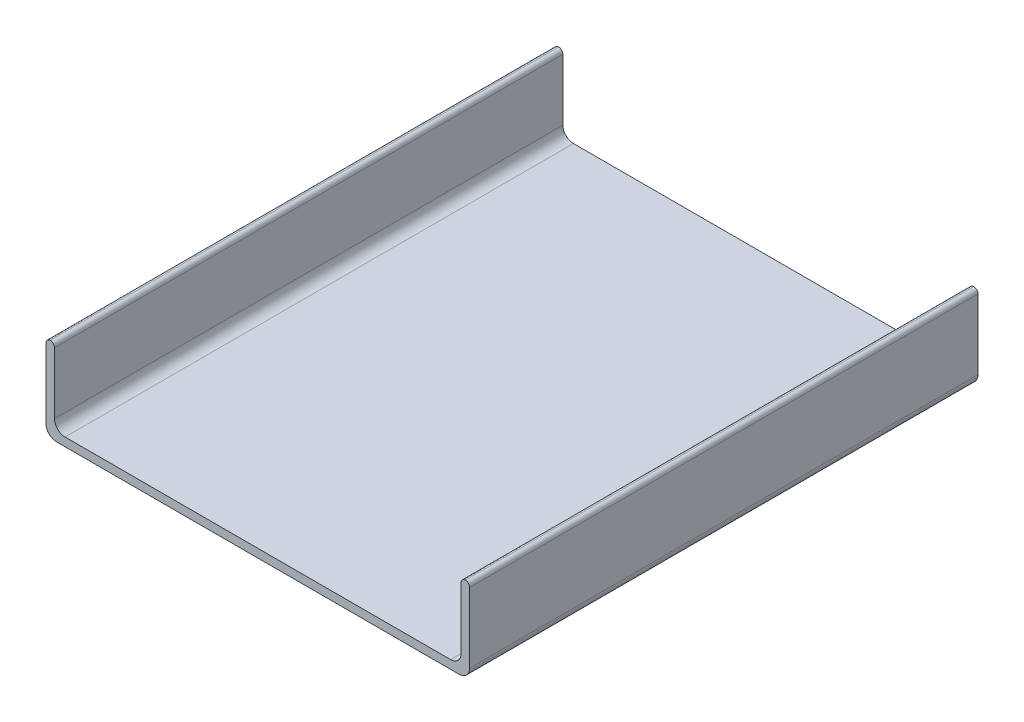
SolidWorks part; units mm, degrees
ref_plane "Front Plane" through (0, 0, 0) normal (0, 0, 1) x (1, 0, 0)
ref_plane "Top Plane" through (0, 0, 0) normal (0, 1, 0) x (1, 0, 0)
ref_plane "Right Plane" through (0, 0, 0) normal (1, 0, 0) x (0, 0, -1)
sketch "Sketch5" plane through (0, 0, 0) normal (0, 0, 1) x (1, 0, 0)
  line L1 (-2.6896, 0.9558) -> (88.3104, 0.9558)
  line L2 (-7.1896, 2.9558) -> (-7.1896, 1.4558)
  line L3 (-4.6896, -1.0442) -> (90.3104, -1.0442)
  line L4 (92.8104, 2.9558) -> (92.8104, 1.4558)
  line L6 (-7.1896, 2.9558) -> (-7.1896, 18.9558)
  line L7 (-7.1896, 18.9558) -> (-5.1896, 18.9558)
  line L8 (-5.1896, 3.4558) -> (-5.1896, 18.9558)
  line L10 (92.8104, 2.9558) -> (92.8104, 18.9558)
  line L11 (92.8104, 18.9558) -> (90.8104, 18.9558)
  line L12 (90.8104, 3.4558) -> (90.8104, 18.9558)
  arc A0 (88.3104, 0.9558) -> (90.8104, 3.4558) centre (88.3104, 3.4558) ccw
  arc A1 (-2.6896, 0.9558) -> (-5.1896, 3.4558) centre (-2.6896, 3.4558) cw
  arc A2 (90.3104, -1.0442) -> (92.8104, 1.4558) centre (90.3104, 1.4558) ccw
  arc A3 (-7.1896, 1.4558) -> (-4.6896, -1.0442) centre (-4.6896, 1.4558) ccw
  point P10 (0, 0)
  point P17 (92.8104, -1.0442)
  point P20 (-7.1896, -1.0442)
  point P21 (0, 0)
  point P22 (0, 0)
  dimension "D7" = 2.5
  dimension "D1" = 4
  dimension "D2" = 100
  dimension "D3" = 20
  dimension "D4" = 20
  dimension "D5" = 2
  dimension "D6" = 2
  dimension "D8" = 2
extrude "Boss-Extrude3" add sketch "Sketch5" along normal blind 120
fillet "Fillet4" radius 1 4 edges at (92.8104, 18.9558, 60) (90.8104, 18.9558, 60) (-7.1896, 18.9558, 60) (-5.1896, 18.9558, 60)
